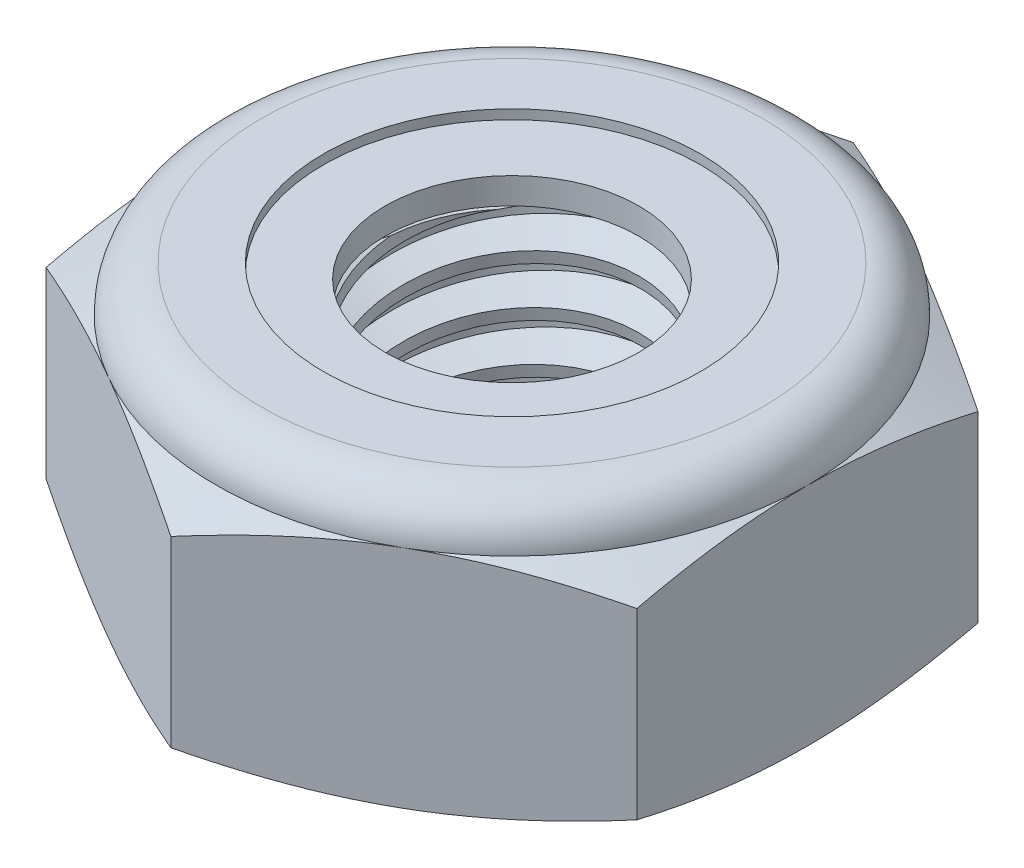
SolidWorks part; units mm, degrees
ref_plane "Front" through (0, 0, 0) normal (0, 0, 1) x (1, 0, 0)
ref_plane "Top" through (0, 0, 0) normal (0, 1, 0) x (1, 0, 0)
ref_plane "Right" through (0, 0, 0) normal (1, 0, 0) x (0, 0, -1)
sketch "Sketch1" plane through (0, 0, 0) normal (0, 1, 0) x (1, 0, 0)
  line L1 (0, 5.4993) -> (-4.7625, 2.7496)
  line L2 (-4.7625, 2.7496) -> (-4.7625, -2.7496)
  line L3 (-4.7625, -2.7496) -> (0, -5.4993)
  line L4 (0, -5.4993) -> (4.7625, -2.7496)
  line L5 (4.7625, -2.7496) -> (4.7625, 2.7496)
  line L6 (4.7625, 2.7496) -> (0, 5.4993)
  circle A0 centre (0, 0) radius 4.7625 construction
  dimension "Hex Flats" = 9.525
extrude "Extrude1" add sketch "Sketch1" along normal blind 4.3656
sketch "Sketch2" plane through (0, 0, 0) normal (1, 0, 0) x (0, 0, -1)
  line L0 (-2.413, 0) -> (-2.413, 4.3656) construction
  line L1 (0, 0) -> (2.413, 0)
  line L2 (0, 0) -> (0, 4.3656)
  line L3 (0, 4.3656) -> (2.413, 4.3656)
  line L4 (2.413, 0) -> (2.413, 4.3656)
  line L5 (-2.7496, 4.3656) -> (2.7496, 4.3656) construction
  line L7 (0, -2.413) -> (0, 0) construction
  dimension "Thread Dia" = 4.826
revolve "Revolve1" add sketch "Sketch2" angle 360 about L7
sketch "Sketch3" plane through (0, 0, 0) normal (1, 0, 0) x (0, 0, -1)
  line L0 (2.413, 4.3656) -> (-2.413, 4.3656) construction
  line L1 (-2.413, 4.3656) -> (-2.413, 3.5719) construction
  line L2 (-2.413, 3.5719) -> (2.413, 4.3656) construction
  line L3 (2.413, 4.3656) -> (2.4291, 4.2677) construction
  line L4 (2.4291, 4.2677) -> (2.5418, 3.5824)
  line L5 (2.5418, 3.5824) -> (2.0776, 3.7574)
  line L6 (2.0776, 3.7574) -> (2.0454, 3.9532)
  line L7 (2.0454, 3.9532) -> (2.4291, 4.2677)
  line L8 (2.0615, 3.8553) -> (2.4855, 3.9251) construction
  line L9 (2.413, 4.3656) -> (2.413, 3.9131) construction
  line L10 (2.413, 3.9131) -> (-2.413, 3.1194) construction
  line L11 (-2.413, 3.1194) -> (-2.413, 3.5719) construction
  line L12 (-0.1397, 4.3656) -> (0.1397, 2.6669) construction
  line L13 (-2.413, 0) -> (-2.413, 4.3656) construction
  line L14 (0, 4.3656) -> (2.413, 4.3656) construction
  line L15 (2.413, 0) -> (2.413, 4.3656) construction
  point P13 (0, 3.5163)
  dimension "D1" = 0.0992
  dimension "D2" = 0.1984
  dimension "Thread Pitch" = 0.7937
  dimension "D4" = 60
  dimension "D5" = 0.7937
revolve "Cut-Revolve1" cut sketch "Sketch3" angle 360 about L12
pattern_linear "LPattern1" count 6 spacing 0.7937 along (0, -1, 0) count 2 spacing 0.7937 along (0, 1, 0) of "Cut-Revolve1"
sketch "Sketch4" plane through (0, 0, 0) normal (1, 0, 0) x (0, 0, -1)
  line L0 (0, 4.3656) -> (2.413, 4.3656)
  line L1 (2.413, 4.3656) -> (2.0454, 4.1942)
  line L2 (2.0454, 4.1942) -> (2.0454, 0.1714)
  line L3 (2.0454, 0.1714) -> (2.413, 0)
  line L4 (2.413, 0) -> (0, 0)
  line L5 (0, 0) -> (0, 4.3656)
  line L6 (2.413, 0) -> (2.413, 4.3656) construction
  line L7 (0, 4.3656) -> (2.413, 4.3656) construction
  line L8 (0, 0) -> (2.413, 0) construction
  line L9 (0, 0) -> (0, 4.3656) construction
  line L10 (0, 4.3656) -> (0, 4.7712) construction
  dimension "D1" = 25
revolve "Cut-Revolve2" cut sketch "Sketch4" angle 360 about L10
combine bodies "Combine1" operation type subtract main body 112 bodies to subtract 111
sketch "Sketch5" plane through (0, 0, 0) normal (1, 0, 0) x (0, 0, -1)
  line L0 (0, 0) -> (4.7625, 0)
  line L1 (4.7625, 0) -> (5.4993, 0.3436)
  line L2 (5.4993, 0.3436) -> (5.4993, 3.2945)
  line L3 (5.4993, 3.2945) -> (4.7625, 3.638)
  line L4 (4.0349, 4.3656) -> (4.0349, 5.6356)
  line L5 (4.0349, 5.6356) -> (6.7693, 5.6356)
  line L6 (6.7693, 5.6356) -> (6.7693, -1.27)
  line L7 (6.7693, -1.27) -> (0, -1.27)
  line L8 (0, -1.27) -> (0, 0)
  line L9 (4.7625, 3.638) -> (4.7625, 0) construction
  line L10 (0, 0) -> (2.413, 0) construction
  line L13 (5.4993, 1.819) -> (6.7693, 1.819) construction
  line L14 (5.4993, 4.3656) -> (5.4993, 0) construction
  line L15 (0, 0) -> (0, 5.6356) construction
  line L20 (0, 5.6356) -> (4.0349, 5.6356) construction
  line L22 (0, 4.3656) -> (2.413, 4.3656) construction
  arc A0 (4.7625, 3.638) -> (4.0349, 4.3656) centre (4.0349, 3.638) ccw
  dimension "D1" = 25
  dimension "D2" = 1.27
  dimension "D3" = 4.3656
  dimension "D4" = 0.7276
revolve "Cut-Revolve3" cut sketch "Sketch5" angle 360 about L15
sketch "Sketch6" plane through (0, 0, 0) normal (1, 0, 0) x (0, 0, -1)
  line L0 (0, 3.638) -> (4.6101, 3.638)
  line L1 (4.0349, 4.2132) -> (3.0402, 4.2132)
  line L2 (0, 5.6356) -> (0, 3.638)
  line L3 (3.0402, 5.6356) -> (0, 5.6356)
  line L4 (0, 5.6356) -> (4.0349, 5.6356) construction
  line L5 (0, 0) -> (0, 5.6356) construction
  line L6 (0, 5.6356) -> (0, 44.323) construction
  line L7 (3.0402, 4.2132) -> (3.0402, 5.6356)
  line L8 (4.0349, 4.3656) -> (4.0349, 4.2132) construction
  line L9 (3.0402, 4.2132) -> (2.0454, 4.2132) construction
  line L10 (2.0454, 4.2132) -> (2.0454, 4.1942) construction
  arc A0 (4.6101, 3.638) -> (4.0349, 4.2132) centre (4.0349, 3.638) ccw
  arc A1 (4.7625, 3.638) -> (4.0349, 4.3656) centre (4.0349, 3.638) ccw construction
  dimension "D1" = 0.1524
revolve "Cut-Revolve4" cut sketch "Sketch6" angle 360 about L6
sketch "Sketch7" plane through (0, 0, 0) normal (1, 0, 0) x (0, 0, -1)
  line L0 (2.0454, 3.7142) -> (4.528, 3.7142)
  line L1 (4.0349, 4.137) -> (2.0454, 4.137)
  line L2 (2.0454, 4.137) -> (2.0454, 3.7142)
  line L3 (2.0454, 3.7142) -> (0, 3.7142) construction
  line L4 (0, 3.7142) -> (0, 4.137) construction
  line L5 (0, 4.137) -> (2.0454, 4.137) construction
  line L6 (2.0454, 3.7142) -> (2.0454, 3.638) construction
  line L7 (0, 3.638) -> (4.6101, 3.638) construction
  line L8 (4.0349, 4.137) -> (4.0349, 4.2132) construction
  arc A0 (4.528, 3.7142) -> (4.0349, 4.137) centre (4.0349, 3.638) ccw
  arc A2 (4.6101, 3.638) -> (4.0349, 4.2132) centre (4.0349, 3.638) ccw construction
  dimension "D1" = 0.0762
revolve "Revolve2" add sketch "Sketch7" angle 360 about L4
equation "\"D1@Sketch3\"=\"Thread Pitch@Sketch3\"/8"
equation "\"D2@Sketch3\"=\"Thread Pitch@Sketch3\"/4"
equation "\"D5@Sketch3\"=\"Thread Pitch@Sketch3\""
equation "\"D4@LPattern1\"=\"Thread Pitch@Sketch3\""
equation "\"D3@LPattern1\"=\"Thread Pitch@Sketch3\""
equation "\"D1@LPattern1\"=\"Height@Extrude1\"/\"Thread Pitch@Sketch3\""
equation "\"D4@Sketch5\"=\"Height@Extrude1\"/6"
